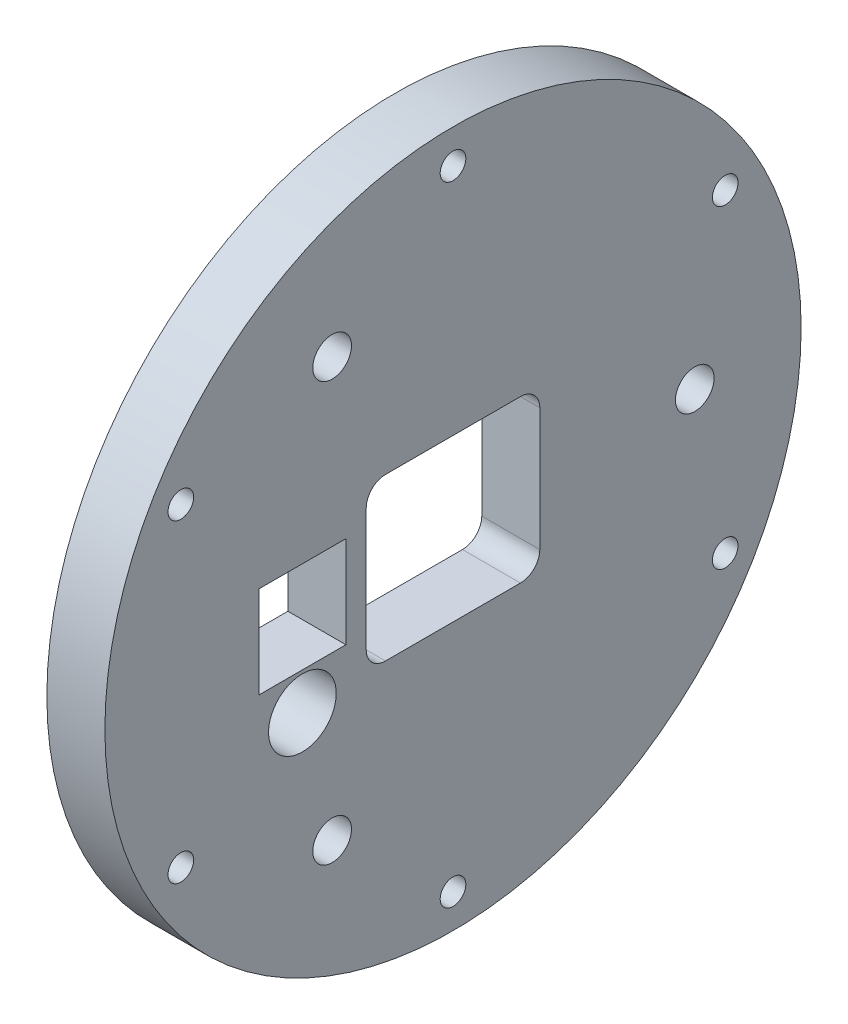
SolidWorks part; units mm, degrees
ref_plane "Front Plane" through (0, 0, 0) normal (0, 0, 1) x (1, 0, 0)
ref_plane "Top Plane" through (0, 0, 0) normal (0, 1, 0) x (1, 0, 0)
ref_plane "Right Plane" through (0, 0, 0) normal (1, 0, 0) x (0, 0, -1)
sketch "Sketch4" plane through (0, 0, 0) normal (1, 0, 0) x (0, 0, -1)
  circle A0 centre (0, 0) radius 72
  dimension "D1" = 144
sketch "Sketch2" plane through (0, 0, 0) normal (1, 0, 0) x (0, 0, -1)
  line L0 (0, 0) -> (0, 77.0354) construction
  circle A0 centre (0, 0) radius 65 construction
  circle A1 centre (0, 65) radius 2.65
  circle A2 centre (56.2917, 32.5) radius 2.65
  circle A3 centre (56.2917, -32.5) radius 2.65
  circle A4 centre (0, -65) radius 2.65
  circle A5 centre (-56.2917, -32.5) radius 2.65
  circle A6 centre (-56.2917, 32.5) radius 2.65
  point P17 (0, 0)
  dimension "D3" = 5.3
  dimension "D1" = 65
  dimension "D2" = 6
sketch "Sketch3" plane through (0, 0, 0) normal (1, 0, 0) x (0, 0, -1)
  line L0 (-4.7792, 0) -> (94.0848, 0) construction
  circle A2 centre (50, 0) radius 4
  circle A3 centre (-25, -43.3013) radius 4
  circle A4 centre (-25, 43.3013) radius 4
  dimension "D1" = 50
  dimension "D3" = 8
  dimension "D5" = 3
extrude "Boss-Extrude3" add sketch "Sketch4" along normal blind 12
extrude "Cut-Extrude6" cut sketch "Sketch3" along normal through all
extrude "Cut-Extrude1" cut sketch "Sketch2" along normal through all
sketch "Sketch1" plane through (0, 0, 0) normal (1, 0, 0) x (0, 0, -1)
  line L0 (-72, 0) -> (72, 0) construction
  line L1 (-13.95, 16.7) -> (13.95, 16.7)
  line L2 (-17.95, 12.7) -> (-17.95, -12.7)
  line L3 (-13.95, -16.7) -> (13.95, -16.7)
  line L4 (17.95, 12.7) -> (17.95, -12.7)
  line L5 (72.7609, -17.4) -> (-66.8201, -17.4) construction
  line L6 (-31.15, -17.4) -> (-31.15, 22.2578) construction
  line L7 (-40.15, 9.3) -> (-22.15, 9.3)
  line L8 (-40.15, 9.3) -> (-40.15, -9.7)
  line L9 (-40.15, -9.7) -> (-22.15, -9.7)
  line L10 (-22.15, 9.3) -> (-22.15, -9.7)
  line L11 (0, 8.4141) -> (0, -10.5859) construction
  line L12 (0, 0) -> (-23.1273, 0) construction
  circle A1 centre (-31.15, -17.4) radius 7
  arc A5 (-13.95, -16.7) -> (-17.95, -12.7) centre (-13.95, -12.7) cw
  arc A6 (13.95, -16.7) -> (17.95, -12.7) centre (13.95, -12.7) ccw
  arc A7 (17.95, 12.7) -> (13.95, 16.7) centre (13.95, 12.7) ccw
  arc A8 (-13.95, 16.7) -> (-17.95, 12.7) centre (-13.95, 12.7) ccw
  point P13 (-13.95, 16.7)
  point P29 (-17.95, -16.7)
  point P32 (17.95, -16.7)
  point P35 (17.95, 16.7)
  point P38 (-17.95, 16.7)
  dimension "D2" = 35.9
  dimension "D7" = 14
  dimension "D12" = 4
  dimension "D6" = 33.4
  dimension "D8" = 13.2
  dimension "D9" = 18
  dimension "D10" = 19
  dimension "D11" = 7.7
  dimension "D13" = 0.7
extrude "gopro" cut sketch "Sketch1" along normal through all
